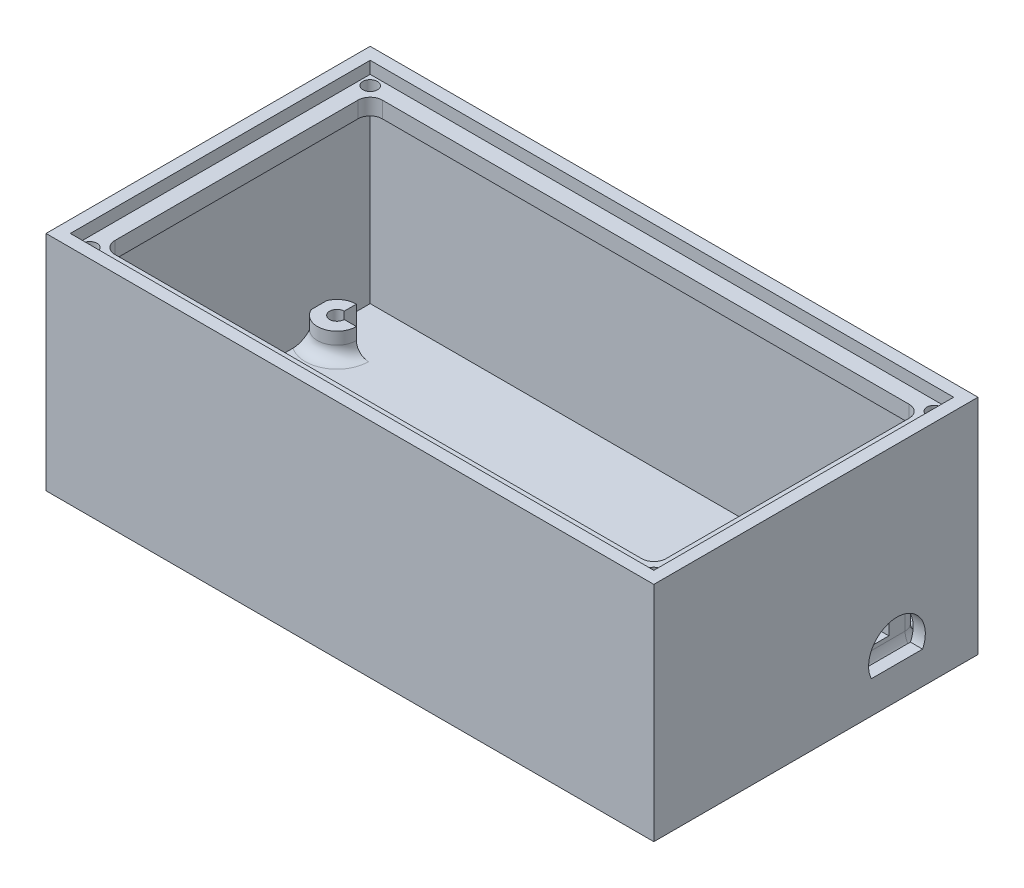
SolidWorks part; units mm, degrees
ref_plane "Front Plane" through (0, 0, 0) normal (0, 0, 1) x (1, 0, 0)
ref_plane "Top Plane" through (0, 0, 0) normal (0, 1, 0) x (1, 0, 0)
ref_plane "Right Plane" through (0, 0, 0) normal (1, 0, 0) x (0, 0, -1)
sketch "Sketch1" plane through (0, 0, 0) normal (0, 1, 0) x (1, 0, 0)
  line L1 (0, 0) -> (75, 0)
  line L2 (0, 0) -> (0, 40)
  line L3 (0, 40) -> (75, 40)
  line L4 (75, 0) -> (75, 40)
  dimension "D1" = 75
  dimension "D2" = 40
extrude "Boss-Extrude1" add sketch "Sketch1" along normal blind 1.5
sketch "Sketch2" plane through (0, 1.5, 0) normal (0, 1, 0) x (1, 0, 0)
  line L0 (1.5, 38.5) -> (1.5, 1.5)
  line L1 (0, 40) -> (75, 40)
  line L2 (0, 40) -> (0, 0)
  line L3 (0, 0) -> (75, 0)
  line L4 (75, 40) -> (75, 0)
  line L5 (1.5, 1.5) -> (73.5, 1.5)
  line L6 (73.5, 38.5) -> (73.5, 1.5)
  line L7 (1.5, 38.5) -> (73.5, 38.5)
  dimension "D1" = 1.5
extrude "Boss-Extrude2" add sketch "Sketch2" along normal blind 26
sketch "Sketch3" plane through (0, 0, 0) normal (-1, 0, 0) x (0, 0, 1)
  line L0 (-40, 1.5) -> (0, 1.5) construction
  line L1 (-40, 27.5) -> (-40, 0) construction
  line L2 (0, 27.5) -> (0, 0) construction
  line L3 (-40, 0) -> (0, 0) construction
  line L5 (-24.5, 1.5) -> (-15.5, 1.5)
  line L6 (-24.5, 1.5) -> (-24.5, 5)
  line L7 (-24.5, 5) -> (-15.5, 5)
  line L8 (-15.5, 1.5) -> (-15.5, 5)
  dimension "D1" = 1.5
  dimension "D2" = 9
  dimension "D3" = 3.5
  dimension "D4" = 15.5
  dimension "D5" = 15.5
extrude "Cut-Extrude1" cut sketch "Sketch3" against normal blind 25
fillet "Fillet1" radius 1 2 edges at (0.75, 5, -24.5) (0.75, 5, -15.5)
sketch "Sketch4" plane through (0, 1.5, 0) normal (0, 1, 0) x (1, 0, 0)
  line L0 (1.5, 20) -> (73.5, 20) construction
  line L1 (1.5, 38.5) -> (1.5, 1.5) construction
  line L2 (73.5, 1.5) -> (73.5, 38.5) construction
  line L3 (1.5, 38.5) -> (1.5, 24.5) construction
  line L4 (1.7, 34.2) -> (56.6, 34.2) construction
  line L5 (1.7, 34.2) -> (1.7, 5.8) construction
  line L6 (1.7, 5.8) -> (56.6, 5.8) construction
  line L7 (56.6, 34.2) -> (56.6, 5.8) construction
  line L8 (4.6, 32.2) -> (6.1, 32.2)
  line L9 (3.7, 33.1) -> (3.7, 34.6)
  line L10 (54.6, 33.1) -> (54.6, 34.6)
  line L11 (3.7, 6.9) -> (3.7, 5.4)
  line L12 (4.6, 7.8) -> (6.1, 7.8)
  line L13 (54.6, 6.9) -> (54.6, 5.4)
  line L14 (52.2, 32.2) -> (53.7, 32.2)
  line L15 (52.2, 7.8) -> (53.7, 7.8)
  arc A0 (3.7, 33.1) -> (4.6, 32.2) centre (3.7, 32.2) ccw
  arc A1 (4.6, 7.8) -> (3.7, 6.9) centre (3.7, 7.8) ccw
  arc A2 (54.6, 6.9) -> (53.7, 7.8) centre (54.6, 7.8) ccw
  arc A3 (53.7, 32.2) -> (54.6, 33.1) centre (54.6, 32.2) ccw
  arc A4 (3.7, 34.6) -> (6.1, 32.2) centre (3.7, 32.2) ccw
  arc A5 (6.1, 7.8) -> (3.7, 5.4) centre (3.7, 7.8) ccw
  arc A6 (54.6, 5.4) -> (52.2, 7.8) centre (54.6, 7.8) ccw
  arc A7 (52.2, 32.2) -> (54.6, 34.6) centre (54.6, 32.2) ccw
  circle A9 centre (3.7, 32.2) radius 0.9 construction
  circle A10 centre (3.7, 32.2) radius 2.4 construction
  circle A11 centre (54.6, 32.2) radius 2.4 construction
  circle A12 centre (54.6, 32.2) radius 0.9 construction
  circle A13 centre (54.6, 7.8) radius 2.4 construction
  circle A14 centre (3.7, 7.8) radius 2.4 construction
  circle A15 centre (3.7, 7.8) radius 0.9 construction
  circle A16 centre (54.6, 7.8) radius 0.9 construction
  point P11 (6.1, 32.2)
  point P13 (55.4607, 8.0631)
  point P25 (6.1, 7.8)
  point P27 (55.4607, 32.4631)
  point P34 (4.5607, 32.4631)
  point P38 (57, 32.2)
  point P44 (57, 7.8)
  point P48 (4.5607, 8.0631)
  dimension "D3" = 2
  dimension "D1" = 54.9
  dimension "D2" = 28.4
  dimension "D4" = 2
  dimension "D5" = 2
  dimension "D6" = 2
  dimension "D7" = 2
  dimension "D8" = 2
  dimension "D9" = 2
  dimension "D10" = 2
  dimension "D11" = 14.2
  dimension "D12" = 0.2
  dimension "D13" = 1.5
extrude "Boss-Extrude3" add sketch "Sketch4" along normal blind 3
fillet "Fillet2" radius 1.5 4 edges at (56.2971, 1.5, -9.4971) (56.2971, 1.5, -30.5029) (4.1899, 1.5, -10.1495) (4.1899, 1.5, -29.8505)
sketch "Sketch6" plane through (0, 27.5, 0) normal (0, 1, 0) x (1, 0, 0)
  line L0 (3.5, 36.5) -> (3.5, 3.5)
  line L1 (0, 40) -> (75, 40)
  line L2 (0, 40) -> (0, 0)
  line L3 (0, 0) -> (75, 0)
  line L4 (75, 40) -> (75, 0)
  line L5 (3.5, 3.5) -> (71.5, 3.5)
  line L6 (71.5, 36.5) -> (71.5, 3.5)
  line L7 (3.5, 36.5) -> (71.5, 36.5)
  dimension "D2" = 68
  dimension "D1" = 3.5
extrude "Boss-Extrude4" add sketch "Sketch6" along normal blind 2 from offset 3.5 offset against normal yes
fillet "Fillet3" radius 1.5 8 edges at (1.5, 24, -20) (37.5, 24, -1.5) (73.5, 24, -20) (37.5, 24, -38.5) (71.5, 25, -3.5) (71.5, 25, -36.5) (3.5, 25, -3.5) (3.5, 25, -36.5)
sketch "Sketch9" plane through (0, 26, 0) normal (0, 1, 0) x (1, 0, 0)
  line L0 (1.5, 1.5) -> (3.9393, 3.9393) construction
  line L1 (1.5, 38.5) -> (3.9393, 36.0607) construction
  line L2 (73.5, 38.5) -> (71.0607, 36.0607) construction
  line L3 (73.5, 1.5) -> (71.0607, 3.9393) construction
  line L4 (1.5, 1.5) -> (73.5, 1.5) construction
  line L6 (73.5, 1.5) -> (73.5, 38.5) construction
  line L7 (73.5, 38.5) -> (1.5, 38.5) construction
  line L8 (1.5, 38.5) -> (1.5, 1.5) construction
  line L9 (1.5, 1.5) -> (73.5, 1.5) construction
  circle A0 centre (2.7, 37.3) radius 0.9
  circle A1 centre (2.7, 2.7) radius 0.9
  circle A2 centre (72.3, 2.7) radius 0.9
  circle A3 centre (72.3, 37.3) radius 0.9
  arc A4 (3.5, 5) -> (5, 3.5) centre (5, 5) ccw construction
  arc A5 (5, 36.5) -> (3.5, 35) centre (5, 35) ccw construction
  arc A6 (71.5, 35) -> (70, 36.5) centre (70, 35) ccw construction
  arc A7 (70, 3.5) -> (71.5, 5) centre (70, 5) ccw construction
  dimension "D1" = 1.2
  dimension "D2" = 1.2
  dimension "D3" = 1.2
  dimension "D4" = 1.2
  dimension "D5" = 1.2
  dimension "D6" = 1.2
  dimension "D7" = 1.2
  dimension "D8" = 1.2
extrude "Cut-Extrude3" cut sketch "Sketch9" against normal blind 4
sketch "Sketch5" plane through (75, 0, 0) normal (1, 0, 0) x (0, 0, -1)
  line L0 (40, 27.5) -> (40, 0) construction
  line L1 (26.5, 5.5) -> (33.5, 5.5) construction
  line L2 (0, 0) -> (40, 0) construction
  line L5 (0, 4) -> (40, 4)
  line L6 (26.8377, 4) -> (33.1623, 4)
  arc A0 (33.1623, 4) -> (26.8377, 4) centre (30, 5.5) ccw
  dimension "D1" = 5.5
  dimension "D3" = 4
  dimension "D2" = 10
extrude "Cut-Extrude2" cut sketch "Sketch5" against normal blind 3
sketch "Sketch10" plane through (0, 1.5, 0) normal (0, 1, 0) x (1, 0, 0)
  line L0 (73.5, 38.5) -> (1.5, 38.5) construction
  line L1 (71.5, 34.5) -> (71.5, 25.5028)
  line L3 (68.3, 34.5) -> (68.2945, 25.5)
  line L4 (71.5, 5) -> (71.5, 35) construction
  line L5 (68.3, 34.5) -> (68.3, 34.502)
  arc A0 (71.5, 34.5) -> (68.3, 34.502) centre (69.9, 34.5) ccw
  arc A1 (68.2945, 25.5) -> (71.5, 25.5028) centre (69.8973, 25.5) ccw
  circle A2 centre (69.9, 34.5) radius 0.85
  circle A3 centre (69.8973, 25.5) radius 0.85
  dimension "D1" = 4
  dimension "D3" = 1.6
  dimension "D4" = 1.7
  dimension "D2" = 9
extrude "Boss-Extrude5" add sketch "Sketch10" along normal offset from surface (4.5 mm away) 2 up to face at (74.25, 4, -30) offset beyond the face yes
fillet "Fillet4" radius 2 4 edges at (69.901, 1.5, -36.1) (71.5, 1.5, -30.0014) (69.8987, 1.5, -23.8973) (68.2973, 1.5, -30.001)
sketch "Sketch11" plane through (0, 6, 0) normal (0, 1, 0) x (1, 0, 0)
  line L3 (68.2976, 27.5014) -> (68.2976, 27.501)
  line L6 (71.4997, 32.5014) -> (71.4997, 32.501)
  line L8 (67.9689, 32.501) -> (71.7496, 32.501)
  line L9 (67.9689, 32.501) -> (67.9689, 27.5014)
  line L10 (67.9689, 27.5014) -> (71.7496, 27.5014)
  line L11 (71.7496, 32.501) -> (71.7496, 27.5014)
  line M3 (71.5, 25.5028) -> (71.5, 34.5)
  line M5 (68.3, 34.502) -> (68.2945, 25.5)
extrude "Cut-Extrude6" cut sketch "Sketch11" against normal blind 2 contours L10 M5 M3 region at (69.8986, 6, -30.0008)
